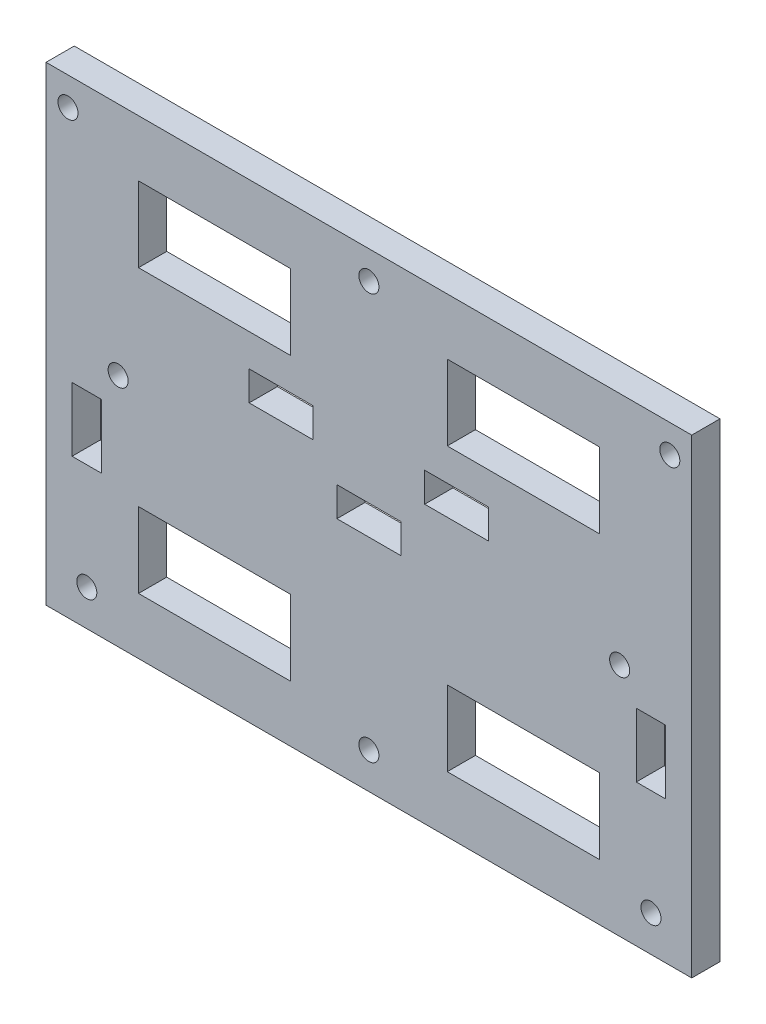
SolidWorks part; units mm, degrees
ref_plane "Front Plane" through (0, 0, 0) normal (0, 0, 1) x (1, 0, 0)
ref_plane "Top Plane" through (0, 0, 0) normal (0, 1, 0) x (1, 0, 0)
ref_plane "Right Plane" through (0, 0, 0) normal (1, 0, 0) x (0, 0, -1)
sketch "Sketch1" plane through (0, 0, 0) normal (0, 0, 1) x (1, 0, 0)
  line L0 (0, -37.5) -> (0, 37.5) construction
  line L1 (-51.5, -37.5) -> (51.5, -37.5)
  line L2 (-51.5, -37.5) -> (-51.5, 37.5)
  line L3 (-51.5, 37.5) -> (51.5, 37.5)
  line L4 (51.5, -37.5) -> (51.5, 37.5)
  line L5 (-51.5, -37.5) -> (51.5, 37.5) construction
  line L6 (-51.5, 37.5) -> (51.5, -37.5) construction
  line L7 (-51.5, 0) -> (51.5, 0) construction
  line L8 (-51.5, 22.5) -> (51.5, 22.5) construction
  line L9 (36.75, 16.5) -> (12.5, 28.5) construction
  line L10 (-36.75, 28.5) -> (-12.5, 28.5)
  line L11 (-36.75, 28.5) -> (-36.75, 16.5)
  line L12 (-36.75, 16.5) -> (-12.5, 16.5)
  line L13 (-12.5, 28.5) -> (-12.5, 16.5)
  line L14 (-36.75, 28.5) -> (-12.5, 16.5) construction
  line L15 (-36.75, 16.5) -> (-12.5, 28.5) construction
  line L16 (36.75, 28.5) -> (12.5, 16.5) construction
  line L17 (12.5, 28.5) -> (12.5, 16.5)
  line L18 (36.75, 16.5) -> (12.5, 16.5)
  line L19 (36.75, 28.5) -> (36.75, 16.5)
  line L20 (36.75, 28.5) -> (12.5, 28.5)
  line L21 (36.75, -28.5) -> (12.5, -16.5) construction
  line L22 (-36.75, -16.5) -> (-12.5, -28.5) construction
  line L23 (-36.75, -28.5) -> (-12.5, -16.5) construction
  line L24 (36.75, -16.5) -> (12.5, -28.5) construction
  line L25 (36.75, -28.5) -> (12.5, -28.5)
  line L26 (36.75, -28.5) -> (36.75, -16.5)
  line L27 (36.75, -16.5) -> (12.5, -16.5)
  line L28 (12.5, -28.5) -> (12.5, -16.5)
  line L29 (-12.5, -28.5) -> (-12.5, -16.5)
  line L30 (-36.75, -16.5) -> (-12.5, -16.5)
  line L31 (-36.75, -28.5) -> (-36.75, -16.5)
  line L32 (-36.75, -28.5) -> (-12.5, -28.5)
  point P0 (0, 0)
  point P12 (-24.625, 22.5)
  point P21 (24.625, 22.5)
  point P30 (24.625, -22.5)
  point P31 (-24.625, -22.5)
  dimension "D1" = 103
  dimension "D2" = 75
  dimension "D3" = 22.5
  dimension "D4" = 24.25
  dimension "D5" = 12
  dimension "D6" = 12.5
extrude "Boss-Extrude1" add sketch "Sketch1" along normal blind 4.5
sketch "Sketch2" plane through (0, 0, 4.5) normal (0, 0, 1) x (1, 0, 0)
  line L0 (0, -37.5) -> (0, 37.5) construction
  line L1 (-51.5, -37.5) -> (51.5, -37.5) construction
  line L2 (51.5, 37.5) -> (-51.5, 37.5) construction
  line L3 (-51.5, 0) -> (51.5, 0) construction
  line L4 (-51.5, 37.5) -> (-51.5, -37.5) construction
  line L5 (51.5, -37.5) -> (51.5, 37.5) construction
  line L6 (-40, 0) -> (40, 0) construction
  line L7 (-48, 33) -> (48, 33) construction
  circle A0 centre (-48, 33) radius 1.6
  circle A1 centre (48, 33) radius 1.6
  circle A2 centre (40, 0) radius 1.6
  circle A3 centre (-40, 0) radius 1.6
  circle A4 centre (0, 33) radius 1.6
  dimension "D1" = 3.2
  dimension "D7" = 3.2
  dimension "D8" = 3.2
  dimension "D9" = 3.2
  dimension "D2" = 48
  dimension "D3" = 33
  dimension "D4" = 80
  dimension "D5" = 40
  dimension "D6" = 0
extrude "screwHoles" cut sketch "Sketch2" against normal through all
sketch "Sketch3" plane through (0, 0, 4.5) normal (0, 0, 1) x (1, 0, 0)
  line L0 (-51.5, 9) -> (26.0486, 9) construction
  line L1 (-51.5, 37.5) -> (-51.5, -37.5) construction
  line L3 (0, 37.5) -> (0, -37.5) construction
  line L4 (51.5, 37.5) -> (-51.5, 37.5) construction
  line L5 (-51.5, -37.5) -> (51.5, -37.5) construction
  line L6 (19.1, 6.65) -> (8.9, 11.35) construction
  line L7 (-19.1, 11.35) -> (-8.9, 11.35)
  line L8 (-19.1, 11.35) -> (-19.1, 6.65)
  line L9 (-19.1, 6.65) -> (-8.9, 6.65)
  line L10 (-8.9, 11.35) -> (-8.9, 6.65)
  line L11 (-19.1, 11.35) -> (-8.9, 6.65) construction
  line L12 (-19.1, 6.65) -> (-8.9, 11.35) construction
  line L13 (19.1, 11.35) -> (8.9, 6.65) construction
  line L14 (8.9, 11.35) -> (8.9, 6.65)
  line L15 (19.1, 6.65) -> (8.9, 6.65)
  line L16 (19.1, 11.35) -> (19.1, 6.65)
  line L17 (19.1, 11.35) -> (8.9, 11.35)
  line L18 (-51.5, 37.5) -> (-51.5, -37.5) construction
  point P2 (-51.5, 0)
  point P12 (-14, 9)
  point P21 (14, 9)
  dimension "D1" = 10.2
  dimension "D2" = 4.7
  dimension "D3" = 14
  dimension "D4" = 9
extrude "BeltClamp" cut sketch "Sketch3" against normal through all
sketch "Sketch4" plane through (0, 0, 4.5) normal (0, 0, 1) x (1, 0, 0)
  line L0 (-51.5, 0) -> (51.5, 0) construction
  line L1 (-51.5, 37.5) -> (-51.5, -37.5) construction
  line L2 (51.5, -37.5) -> (51.5, 37.5) construction
  line L4 (-5.1, 2.35) -> (5.1, 2.35)
  line L5 (-5.1, 2.35) -> (-5.1, -2.35)
  line L6 (-5.1, -2.35) -> (5.1, -2.35)
  line L7 (5.1, 2.35) -> (5.1, -2.35)
  line L8 (-5.1, 2.35) -> (5.1, -2.35) construction
  line L9 (-5.1, -2.35) -> (5.1, 2.35) construction
  circle A0 centre (-40, 0) radius 1.6 construction
  point P6 (0, 0)
  dimension "D1" = 10.2
  dimension "D2" = 4.7
  dimension "D3" = 0
extrude "Cut-Extrude3" cut sketch "Sketch4" against normal through all
sketch "Sketch5" plane through (0, 0, 4.5) normal (0, 0, 1) x (1, 0, 0)
  line L0 (-51.5, -9.75) -> (51.5, -9.75) construction
  line L1 (-51.5, 37.5) -> (-51.5, -37.5) construction
  line L2 (51.5, -37.5) -> (51.5, 37.5) construction
  line L3 (5.1, -2.35) -> (5.1, 2.35) construction
  line L4 (0, -37.5) -> (0, 37.5) construction
  line L5 (-51.5, -37.5) -> (51.5, -37.5) construction
  line L6 (51.5, 37.5) -> (-51.5, 37.5) construction
  line L7 (-42.65, -14.85) -> (-47.35, -4.65) construction
  line L8 (42.65, -4.65) -> (47.35, -4.65)
  line L9 (42.65, -4.65) -> (42.65, -14.85)
  line L10 (42.65, -14.85) -> (47.35, -14.85)
  line L11 (47.35, -4.65) -> (47.35, -14.85)
  line L12 (42.65, -4.65) -> (47.35, -14.85) construction
  line L13 (42.65, -14.85) -> (47.35, -4.65) construction
  line L14 (-42.65, -4.65) -> (-47.35, -14.85) construction
  line L15 (-47.35, -4.65) -> (-47.35, -14.85)
  line L16 (-42.65, -14.85) -> (-47.35, -14.85)
  line L17 (-42.65, -4.65) -> (-42.65, -14.85)
  line L18 (-42.65, -4.65) -> (-47.35, -4.65)
  line L19 (45, -9.75) -> (45, -37.5) construction
  line L20 (-45, -9.75) -> (-45, -37.5) construction
  line L21 (-45, -31.75) -> (45, -31.75) construction
  circle A0 centre (45, -31.75) radius 1.6
  circle A1 centre (-45, -31.75) radius 1.6
  circle A2 centre (0, -31.75) radius 1.6
  point P6 (5.1, 0)
  point P15 (45, -9.75)
  point P24 (-45, -9.75)
  dimension "D5" = 3.2
  dimension "D7" = 3.2
  dimension "D1" = 9.75
  dimension "D2" = 10.2
  dimension "D3" = 4.7
  dimension "D4" = 45
  dimension "D6" = 22
extrude "Cut-Extrude4" cut sketch "Sketch5" against normal through all
sketch "Sketch6" plane through (0, 0, 4.5) normal (0, 0, 1) x (1, 0, 0)
  line L0 (-47.35, -9.75) -> (47.35, -9.75) construction
  line L1 (-47.35, -4.65) -> (-47.35, -14.85) construction
  line L2 (47.35, -14.85) -> (47.35, -4.65) construction
  line L3 (0, -2.35) -> (0, -37.5) construction
  line L4 (-5.1, -2.35) -> (5.1, -2.35) construction
  line L5 (-51.5, -37.5) -> (51.5, -37.5) construction
  line L6 (45, -14.85) -> (45, -4.65) construction
  line L7 (42.65, -14.85) -> (47.35, -14.85) construction
  line L8 (47.35, -4.65) -> (42.65, -4.65) construction
  line L9 (42.65, -4.65) -> (42.65, -14.85) construction
  line L10 (41.65, -15.85) -> (48.35, -15.85)
  line L11 (41.65, -15.85) -> (41.65, -3.65)
  line L12 (41.65, -3.65) -> (48.35, -3.65)
  line L13 (48.35, -15.85) -> (48.35, -3.65)
  line L14 (41.65, -15.85) -> (48.35, -3.65) construction
  line L15 (41.65, -3.65) -> (48.35, -15.85) construction
  line L16 (-41.65, -3.65) -> (-48.35, -15.85) construction
  line L17 (-41.65, -15.85) -> (-48.35, -3.65) construction
  line L18 (-45, -14.85) -> (-45, -4.65) construction
  line L19 (-48.35, -15.85) -> (-48.35, -3.65)
  line L20 (-41.65, -3.65) -> (-48.35, -3.65)
  line L21 (-41.65, -15.85) -> (-41.65, -3.65)
  line L22 (-41.65, -15.85) -> (-48.35, -15.85)
  circle A0 centre (45, -9.75) radius 1.6
  circle A1 centre (-45, -9.75) radius 1.6
  point P18 (45, -9.75)
  dimension "D3" = 3.2
  dimension "D1" = 1
  dimension "D2" = 1
extrude "FrontToRear1" [suppressed] add sketch "Sketch6" against normal up to surface (4.5 mm away) up to face at (1.6, -31.75, 0)
sketch "Sketch7" plane through (0, 0, 4.5) normal (0, 0, 1) x (1, 0, 0)
  line L0 (5.1, 2.35) -> (-5.1, 2.35) construction
  line L1 (-45, -3.35) -> (45, -3.35)
  line L2 (-45, -3.35) -> (-45, 3.35)
  line L3 (-45, 3.35) -> (45, 3.35)
  line L4 (45, -3.35) -> (45, 3.35)
  line L5 (-45, -3.35) -> (45, 3.35) construction
  line L6 (-45, 3.35) -> (45, -3.35) construction
  circle A0 centre (40, 0) radius 1.6 construction
  point P0 (0, 0)
  dimension "D1" = 1
  dimension "D2" = 5
extrude "FrontToRear2" [suppressed] add sketch "Sketch7" against normal through all
equation "\"X-ROD-SPACING\"=45"
equation "\"Y-ROD-SPACING\"=75"
equation "\"Z-ROD-SPACING\"=17.5"
equation "\"Y-BED-OFFSET\"=2"
equation "\"Y-BED-ROD-INSET\"=3.5"
equation "\"Y-BED-SCREW-SPACING\"=209"
equation "\"Y-BED-SCREW-CUTOUT-SLOT-HEIGHT\"=1"
equation "\"T-SLOT-NUT-FILLET-RADIUS\"=0.25"
equation "\"T-SLOT-SCREW-SHAFT-RADIUS\"=1.75"
equation "\"T-SLOT-SCREW-SHAFT-CUTOUT-LENGTH\"=10.5"
equation "\"T-SLOT-NUT-DEPTH\"=4.2"
equation "\"T-SLOT-NUT-WIDTH\"=3"
equation "\"T-SLOT-NUT-END-DISTANCE\"=8"
equation "\"ACRYLIC-THICKNESS\"=10"
equation "\"ACRYLIC-THICKNESS2\"=4.5"
equation "\"ACRYLIC-TAB-CUTOUT-SIZE\"=\"ACRYLIC-THICKNESS\"+\"ACRYLIC-TAB-TOLERANCE\"*2"
equation "\"ACRYLIC-TAB-WIDTH\"=\"ACRYLIC-THICKNESS\""
equation "\"ACRYLIC-M3-HOLE\"=3.2"
equation "\"SMOOTHROD-CAP-SCREW-DISTANCE\"=20"
equation "\"FRAME-WIDTH-INNER\"=370"
equation "\"NEMA17-HOLE-SPACING\"=31"
equation "\"NEMA17-CENTRAL-CUTOUT\"=22.5"
equation "\"Z-BRACKET-REACH\"=55"
equation "\"Z-ROD-INSET\"=16"
equation "\"TOP-BRACKET-SPACING\"=40"
equation "\"SMOOTHROD-X-LENGTH\"=350"
equation "\"SMOOTHROD-Y-LENGTH\"=350"
equation "\"SMOOTHROD-Z-LENGTH\"=350"
equation "\"SMOOTHROD-TIGHTENING-HEADROOM\"=1"
equation "\"LEADSCREW-Z-LENGTH\"=300"
equation "\"SCREW-LENGTH-FRAME\"=\"ACRYLIC-THICKNESS\" + 10"
equation "\"SCREW-LENGTH-MOTOR\"=\"ACRYLIC-THICKNESS\" + 5"
equation "\"SCREW-HEAD-RADIUS\"=6"
equation "\"PRINTED-X-SMOOTHROD-DIAMETER\"=8.2"
equation "\"PRINTED-X-SMOOTHROD-CUTOUT\"=10"
equation "\"PRINTED-X-BASE-HEIGHT\"=10"
equation "\"PRINTED-LM8UU-CUTOUT-SIZE\"=16"
equation "\"PRINTED-LM8UU-CUTOUT-LENGTH\"=24.5"
equation "\"PRINTED-X-IDLER-HEIGHT\"=16"
equation "\"PSU-MOUNTING-WIDTH\"=95"
equation "\"PSU-MOUNTING-HEIGHT\"=177"
equation "\"Y-BELT-TO-ROD-DISTANCE\"=20"
equation "\"SPOOL-HOLDER-ROD-SPACING\"=150"
equation "\"D3@Sketch1\"=\"X-ROD-SPACING\"/2"
equation "\"D4@Sketch1\"=\"ACRYLIC-X-CARRIAGE-LM8UU-CUTOUT-WIDTH\""
equation "\"D1@Boss-Extrude1\"=\"ACRYLIC-THICKNESS2\""
equation "\"D1@Sketch2\"=\"ACRYLIC-M3-HOLE\""
equation "\"D1@Sketch3\"=\"ACRYLIC-TAB-CUTOUT-SIZE\""
equation "\"D2@Sketch3\"=\"ACRYLIC-THICKNESS2\"+\"ACRYLIC-TAB-TOLERANCE\"*2"
equation "\"ACRYLIC-X-CARRIAGE-WIDTH\"=55"
equation "\"ACRYLIC-X-CARRIAGE-HEIGHT\"=75"
equation "\"D2@Sketch1\"=\"ACRYLIC-X-CARRIAGE-HEIGHT\""
equation "\"ACRYLIC-X-CARRIAGE-CENTER-TAB-SPACING\"=14"
equation "\"D3@Sketch3\"=\"ACRYLIC-X-CARRIAGE-CENTER-TAB-SPACING\""
equation "\"SCREW-LENGTH-EXTRUDER\"=28"
equation "\"ACRYLIC-X-CARRIAGE-SCREW-SPACING-X\"=15"
equation "\"ACRYLIC-X-CARRIAGE-SCREW-SPACING-Y\"=33"
equation "\"D3@Sketch2\"=\"ACRYLIC-X-CARRIAGE-SCREW-SPACING-Y\""
equation "\"D1@Sketch4\"=\"ACRYLIC-TAB-CUTOUT-SIZE\""
equation "\"D2@Sketch4\"=\"ACRYLIC-THICKNESS2\"+\"ACRYLIC-TAB-TOLERANCE\"*2"
equation "\"D2@Sketch5\"=\"ACRYLIC-TAB-CUTOUT-SIZE\""
equation "\"D3@Sketch5\"=\"ACRYLIC-THICKNESS2\"+\"ACRYLIC-TAB-TOLERANCE\"*2"
equation "\"ACRYLIC-X-CARRIAGE-EXTRUDER-SHELF-DEPTH\"=\"ACRYLIC-X-CARRIAGE-EXTRUDER-OFFSET\" + 30"
equation "\"ACRYLIC-X-CARRIAGE-EXTRUDER-BRACE-SPACING\"=23"
equation "\"D4@Sketch5\"=\"ACRYLIC-X-CARRIAGE-DUAL-MOUNT-BRACE-WIDTH\""
equation "\"D1@Sketch5\"=\"ACRYLIC-THICKNESS2\"/2 + 7.5"
equation "\"D4@Sketch2\"=\"ACRYLIC-X-CARRIAGE-DUAL-MOUNT-SCREW-WIDTH\"*2"
equation "\"D5@Sketch2\"=\"ACRYLIC-X-CARRIAGE-DUAL-MOUNT-SCREW-WIDTH\""
equation "\"D7@Sketch2\"=\"ACRYLIC-M3-HOLE\""
equation "\"D8@Sketch2\"=\"ACRYLIC-M3-HOLE\""
equation "\"ACRYLIC-X-CARRIAGE-LM8UU-CUTOUT-WIDTH\"=24.25"
equation "\"ACRYLIC-TAB-TOLERANCE\"=.1"
equation "\"ACRYLIC-X-CARRIAGE-EXTRUDER-OFFSET\"=26"
equation "\"ACRYLIC-X-CARRIAGE-EXTRUDER-ANGLE\"=90"
equation "\"ACRYLIC-X-CARRIAGE-EXTRUDER-BRACE-TAB-OFFSET\"=20"
equation "\"ACRYLIC-X-CARRIAGE-EXTRUDER-BRACE-HEIGHT\"=35"
equation "\"ACRYLIC-X-CARRIAGE-EXTRUDER-BRACE-SCREW-SPACING\"=22"
equation "\"D5@Sketch5\"=\"ACRYLIC-M3-HOLE\""
equation "\"D3@Sketch6\"=\"ACRYLIC-M3-HOLE\""
equation "\"ACRYLIC-X-CARRIAGE-DUAL-WIDTH-MULTIPLIER\"=1.65"
equation "\"ACRYLIC-X-CARRIAGE-DUAL-HOTEND-SPACING\"=42"
equation "\"ACRYLIC-X-CARRIAGE-DUAL-WIDTH\"=103"
equation "\"ACRYLIC-X-CARRIAGE-DUAL-HOTEND-SEPARATION\"=35"
equation "\"ACRYLIC-X-CARRIAGE-DUAL-MOUNT-PLATE-DEPTH\"=76"
equation "\"ACRYLIC-X-CARRIAGE-DUAL-MOUNT-BRACE-WIDTH\"=45"
equation "\"ACRYLIC-X-CARRIAGE-DUAL-MOUNT-SCREW-WIDTH\"=40"
equation "\"D1@Sketch1\"=\"ACRYLIC-X-CARRIAGE-DUAL-WIDTH\""
equation "\"D9@Sketch2\"=\"ACRYLIC-M3-HOLE\""
equation "\"D7@Sketch5\"=\"ACRYLIC-M3-HOLE\""
